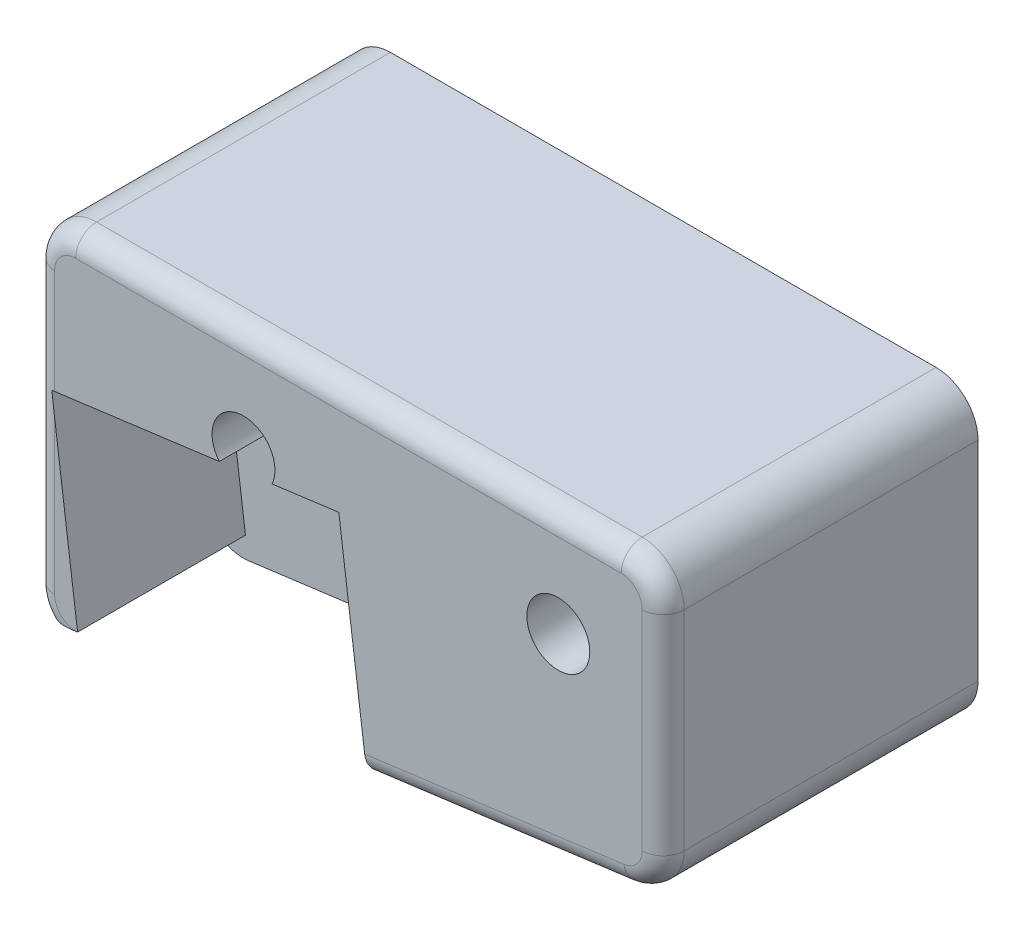
SolidWorks part; units mm, degrees
ref_plane "Front Plane" through (0, 0, 0) normal (0, 0, 1) x (1, 0, 0)
ref_plane "Top Plane" through (0, 0, 0) normal (0, 1, 0) x (1, 0, 0)
ref_plane "Right Plane" through (0, 0, 0) normal (1, 0, 0) x (0, 0, -1)
sketch "Sketch1" plane through (0, 0, 0) normal (0, 0, 1) x (1, 0, 0)
  line L1 (0, 0) -> (30, 0)
  line L2 (0, 0) -> (0, 10)
  line L3 (0, 10) -> (30, 10)
  line L4 (30, 0) -> (30, 10)
  line L7 (10, 5) -> (25, 5) construction
  circle A0 centre (10, 5) radius 1.5
  circle A3 centre (25, 5) radius 1.5
  dimension "D1" = 10
  dimension "D3" = 3
  dimension "D2" = 30
  dimension "D4" = 10
  dimension "D5" = 5
  dimension "D6" = 5
extrude "Boss-Extrude1" add sketch "Sketch1" along normal blind 15
sketch "Sketch2" plane through (0, 0, 15) normal (0, 0, 1) x (1, 0, 0)
  line L1 (30, 0) -> (0, 0)
  line L2 (30, 0) -> (30, -3.7049)
  line L3 (30, -3.7049) -> (0, -7.6545)
  line L4 (0, -7.6545) -> (0, 0)
  line L5 (30, -3.7049) -> (0, -3.7049) construction
  circle A0 centre (10, 5) radius 1.5 construction
  dimension "D2" = 12.6545
  dimension "D1" = 7.5
extrude "Boss-Extrude3" add sketch "Sketch2" against normal through all
sketch "Sketch3" plane through (0, 0, 15) normal (0, 0, 1) x (1, 0, 0)
  line L4 (5, -0.5) -> (11.5, 0.3557) construction
  line L5 (0, -7.6545) -> (30, -3.7049) construction
  line L6 (0, -7.6545) -> (30, -3.7049) construction
  circle A0 centre (10, 5) radius 1.5 construction
  circle A2 centre (5, -0.5) radius 1.1
  circle A3 centre (11.5, 0.3557) radius 1.1
  dimension "D1" = 2.2
  dimension "D3" = 5.5
  dimension "D4" = 5
  dimension "D2" = 6.5
extrude "Cut-Extrude1" cut sketch "Sketch3" against normal through all
sketch "Sketch4" plane through (0, 0, 15) normal (0, 0, 1) x (1, 0, 0)
  line L0 (2.0925, -6.379) -> (0.8591, 2.9894)
  line L1 (0, -7.6545) -> (30, -3.7049) construction
  line L2 (0.8591, 2.9894) -> (14.5411, 4.7906)
  line L3 (14.5411, 4.7906) -> (15.9038, -5.5607)
  line L4 (15.9038, -5.5607) -> (0, -7.6545)
  line L5 (15.2201, -4.1976) -> (14.7371, -0.5293) construction
  line L6 (2.0466, -2.2) -> (2.5296, -5.8684) construction
  line L7 (2.2827, 2.6725) -> (3.175, 2.7899) construction
  line L8 (0, -7.6545) -> (0, -6.6545)
  line L9 (0, 10) -> (0, -7.6545) construction
  line L10 (0, -6.6545) -> (2.0925, -6.379)
  dimension "D1" = 0.5
  dimension "D2" = 0.5
  dimension "D3" = 0.5
  dimension "D4" = 1
extrude "Cut-Extrude2" cut sketch "Sketch4" against normal offset from surface (8 mm away) 7 up to face at (6.1, -0.5, 0)
fillet "Fillet1" radius 2 4 edges at (30, 10, 7.5) (0, 10, 7.5) (0, -7.6545, 3.5) (30, -3.7049, 7.5)
fillet "Fillet2" radius 1 8 edges at (22.0824, -4.7473, 15) (29.5037, -3.2696, 15) (30, 3.0245, 15) (29.4142, 9.4142, 15) (0.1077, -6.0215, 15) (0, 1.313, 15) (0.5858, 9.4142, 15) (15, 10, 15)
sketch "Sketch5" plane through (0, 0, 7) normal (0, 0, 1) x (1, 0, 0)
  line L0 (2.2611, -7.3568) -> (15.9038, -5.5607) construction
  line L1 (8.7924, -6.4969) -> (11.7667, -6.1053)
  arc A0 (6.57, 4.5512) -> (4.43, 2.4488) centre (5.5, 3.5) ccw
  arc A2 (4.43, 2.4488) -> (8.7924, -6.4969) centre (-6.7595, -8.5444) cw
  arc A3 (6.57, 4.5512) -> (11.7667, -6.1053) centre (-6.7595, -8.5444) cw
  circle A4 centre (5, -0.5) radius 1.1 construction
  point P1 (5.5012, 3.3942)
  point P10 (10.924, -6.2163)
  point P13 (8.7924, -6.4969)
  dimension "D1" = 3
  dimension "D2" = 3
  dimension "D3" = 4
  dimension "D4" = 0.5
extrude "Cut-Extrude5" cut sketch "Sketch5" along normal blind 2 and the other way through all
